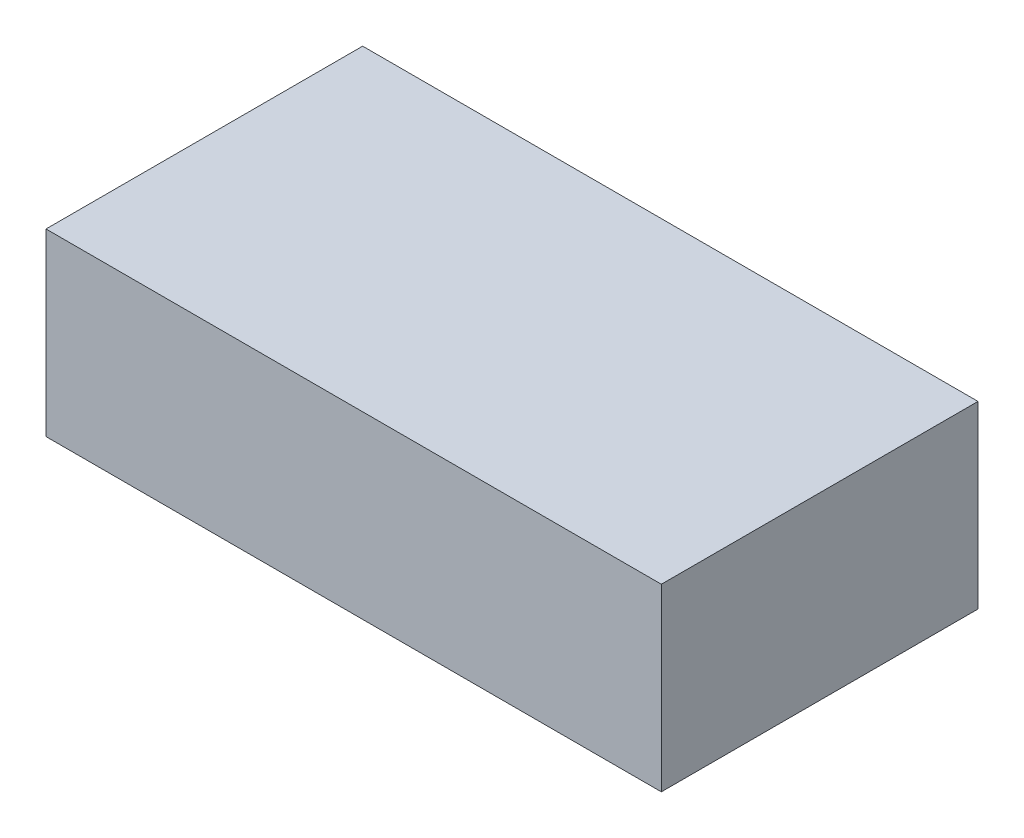
SolidWorks part; units mm, degrees
ref_plane "Front Plane" through (0, 0, 0) normal (0, 0, 1) x (1, 0, 0)
ref_plane "Top Plane" through (0, 0, 0) normal (0, 1, 0) x (1, 0, 0)
ref_plane "Right Plane" through (0, 0, 0) normal (1, 0, 0) x (0, 0, -1)
sketch "Эскиз1" plane through (0, 0, 0) normal (0, 0, 1) x (1, 0, 0)
  line L1 (0, 0) -> (19.4327, 0)
  line L2 (0, 0) -> (0, -5.6784)
  line L3 (0, -5.6784) -> (19.4327, -5.6784)
  line L4 (19.4327, 0) -> (19.4327, -5.6784)
extrude "Бобышка-Вытянуть1" add sketch "Эскиз1" along normal blind 10
